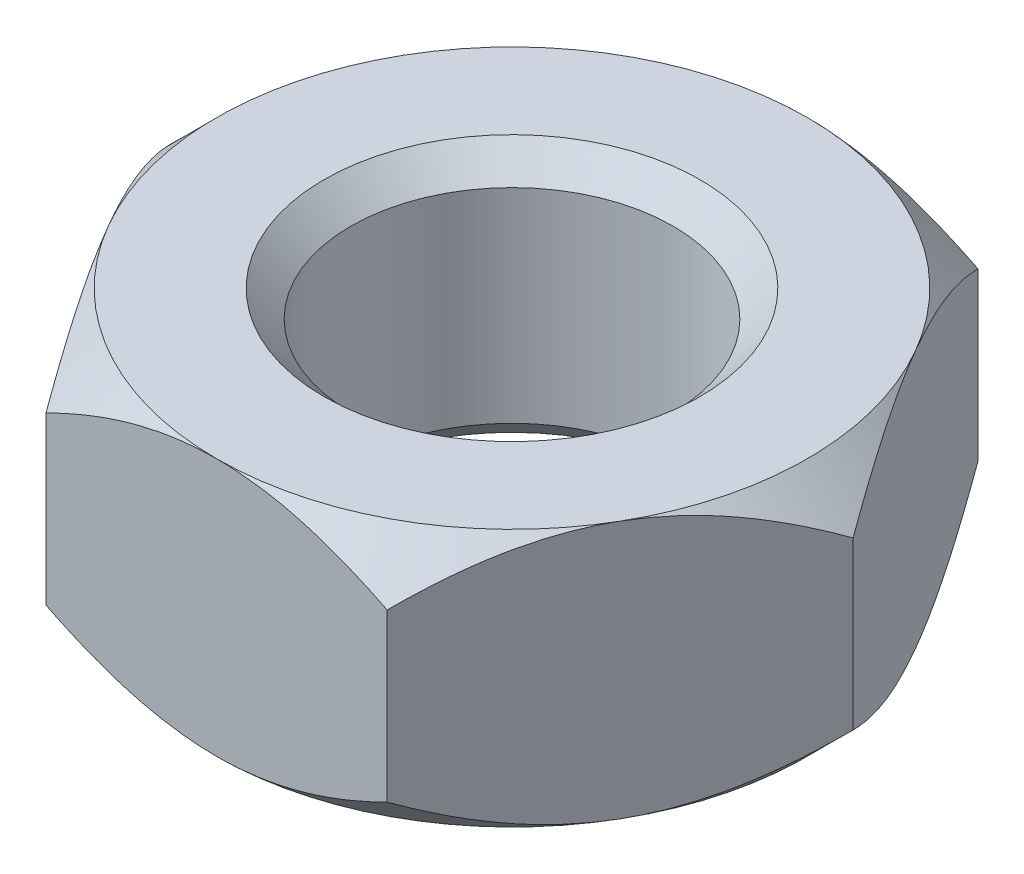
SolidWorks part; units mm, degrees
ref_plane "Front Plane" through (0, 0, 0) normal (0, 0, 1) x (1, 0, 0)
ref_plane "Top Plane" through (0, 0, 0) normal (0, 1, 0) x (1, 0, 0)
ref_plane "Right Plane" through (0, 0, 0) normal (1, 0, 0) x (0, 0, -1)
sketch "Sketch1" plane through (0, 0, 0) normal (0, 1, 0) x (1, 0, 0)
  line L1 (3.1754, 0) -> (1.5877, 2.75)
  line L2 (1.5877, 2.75) -> (-1.5877, 2.75)
  line L3 (-1.5877, 2.75) -> (-3.1754, 0)
  line L4 (-3.1754, 0) -> (-1.5877, -2.75)
  line L5 (-1.5877, -2.75) -> (1.5877, -2.75)
  line L6 (1.5877, -2.75) -> (3.1754, 0)
  circle A0 centre (0, 0) radius 2.75 construction
  circle A1 centre (0, 0) radius 1.5
  dimension "D2" = 3
  dimension "D1" = 5.5
extrude "Boss-Extrude1" add sketch "Sketch1" along normal blind 2.4 contours L5 L6 L1 L2 L3 L4 A1 region at (2.3088, 0, 1.333)
sketch "Sketch2" plane through (0, 0, 0) normal (1, 0, 0) x (0, 0, -1)
  line L0 (2.75, 2.4) -> (3.8, 3.45)
  line L1 (3.8, 3.45) -> (3.8, 1.35)
  line L2 (3.8, 1.35) -> (2.75, 2.4)
  line L3 (2.75, 1.2) -> (7.8632, 1.2) construction
  line L4 (2.75, 2.4) -> (2.75, 0) construction
  line L5 (3.8, 1.05) -> (2.75, 0)
  line L6 (3.8, -1.05) -> (3.8, 1.05)
  line L7 (2.75, 0) -> (3.8, -1.05)
  dimension "D1" = 2.1
ref_axis "Axis1" through (0, 2.4, 0) along (0, -1, 0)
revolve "Cut-Revolve1" cut sketch "Sketch2" angle 360 about axis through (0, 2.4, 0) along (0, -1, 0)
sketch "Sketch4" plane through (0, 2.4, 0) normal (0, 1, 0) x (1, 0, 0)
  circle A0 centre (0, 0) radius 4
curve "Helix/Spiral1" [suppressed] pitch 1.25 height 5 turns 4
ref_plane "Plane1" [suppressed] through (0, 5, 4) normal (-0.9988, -0.0497, 0) x (0, 0, 1)
chamfer "Chamfer1" [suppressed] distance 0.5 angle 45
sketch "Sketch5" [suppressed] plane through (0, 5, 4) normal (-0.9988, -0.0497, 0) x (0, 0, 1)
  line L0 (0.4983, 0.146) -> (-0.8007, 0.896)
  line L1 (-0.8007, 0.896) -> (-0.8007, -0.604)
  line L2 (-0.8007, -0.604) -> (0.4983, 0.146)
  line L3 (-0.0006, -0.854) -> (0.1004, -0.854) construction
  dimension "D1" = 1.5
ref_axis "Axis2" through (0, 2.4, 0) along (0, -1, 0)
chamfer "Chamfer2" distance 0.25 angle 45 2 edges at (0, 2.4, 1.5) (0, 0, 1.5)
